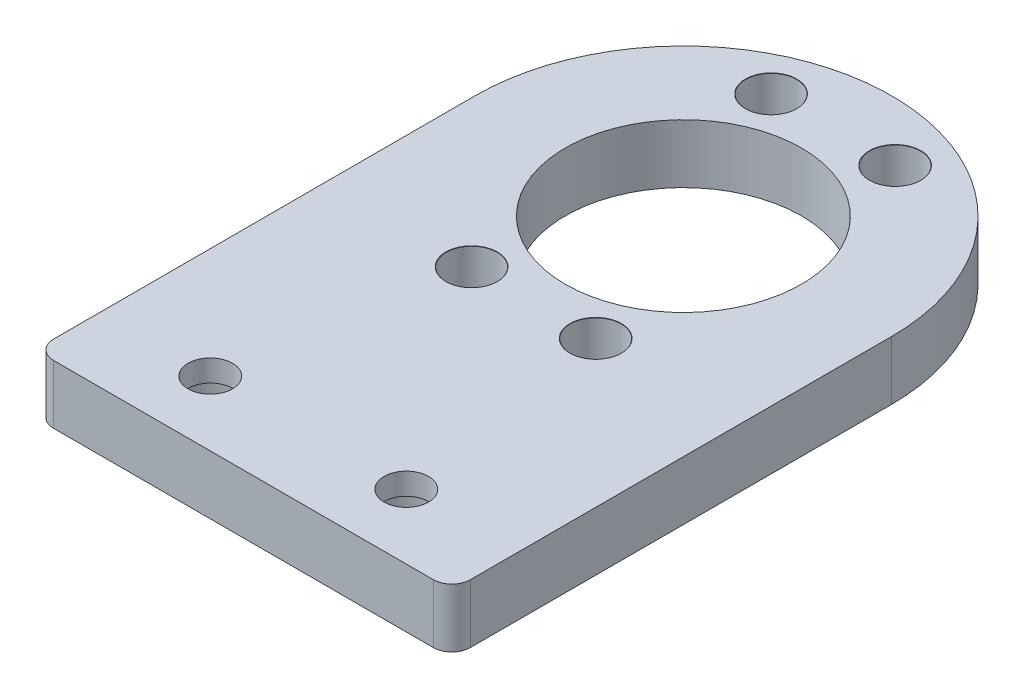
SolidWorks part; units mm, degrees
material "ABS PC"
ref_plane "Front Plane" through (0, 0, 0) normal (0, 0, 1) x (1, 0, 0)
ref_plane "Top Plane" through (0, 0, 0) normal (0, 1, 0) x (1, 0, 0)
ref_plane "Right Plane" through (0, 0, 0) normal (1, 0, 0) x (0, 0, -1)
sketch "Sketch1" plane through (0, 0, 0) normal (0, 1, 0) x (1, 0, 0)
  line L5 (-22.5, -47.5) -> (22.5, -47.5)
  line L6 (-22.5, -47.5) -> (-22.5, 0)
  line L8 (22.5, -47.5) -> (22.5, 0)
  line L9 (-22.5, -47.5) -> (22.5, 0) construction
  line L10 (-22.5, 0) -> (22.5, -47.5) construction
  arc A0 (22.5, 0) -> (-22.5, 0) centre (0, 0) ccw
  point P2 (0, -23.75)
  dimension "D1" = 45
  dimension "D2" = 70
  dimension "D3" = 45
extrude "Boss-Extrude1" add sketch "Sketch1" along normal blind 6.35
sketch "Sketch2" plane through (0, 6.35, 0) normal (0, 1, 0) x (1, 0, 0)
  line L0 (-6.697, 16.1679) -> (6.697, 16.1679) construction
  circle A0 centre (0, 0) radius 17.5 construction
  circle A1 centre (0, 0) radius 17.5 construction
  circle A2 centre (0, 0) radius 17.5 construction
  circle A3 centre (0, 0) radius 17.5 construction
  circle A4 centre (0, 0) radius 17.5 construction
  circle A5 centre (0, 0) radius 17.5 construction
  circle A6 centre (0, 0) radius 17.5 construction
  circle A7 centre (0, 0) radius 17.5 construction
  point P3 (-6.697, 16.1679)
  point P5 (-16.1679, -6.697)
  point P7 (6.697, 16.1679)
  point P9 (16.1679, 6.697)
  point P11 (16.1679, -6.697)
  point P13 (6.697, -16.1679)
  point P15 (-6.697, -16.1679)
  point P16 (0, 0)
  point P18 (-16.1679, 6.697)
  dimension "D1" = 35
  dimension "D2" = 8
hole_wizard "M5 Clearance Hole1" positions "Sketch3" profile "Sketch4" hole size "M5" standard "ANSI Metric" end condition through all
sketch "Sketch3" plane through (0, 6.35, 0) normal (0, 1, 0) x (1, 0, 0)
  point P0 (-6.697, -16.1679)
  point P3 (6.697, -16.1679)
  point P6 (6.697, 16.1679)
  point P15 (-6.697, 16.1679)
sketch "Sketch4" plane through (-6.697, 6.35, 16.1679) normal (1, 0, 0) x (0, 0, 1)
  line L0 (0, 0) -> (0, 6.35)
  line L1 (0, 6.35) -> (2.75, 6.35)
  line L2 (2.75, 6.35) -> (2.75, 0.025)
  line L3 (2.75, 0.025) -> (2.775, 0)
  line L5 (2.775, 0) -> (0, 0)
  line L6 (-2.75, 0.025) -> (-2.775, 0) construction
  line L11 (0, -6.35) -> (0, 107.95) construction
  dimension "Thru Hole Dia." = 5.5
  dimension "Thru Hole Depth" = 6.35
  dimension "Near C'Sink Dia." = 5.55
  dimension "Near C'Sink Angle" = 90
sketch "Sketch5" plane through (0, 6.35, 0) normal (0, 1, 0) x (1, 0, 0)
  circle A0 centre (0, 0) radius 12.75
  dimension "D1" = 25.5
extrude "Cut-Extrude1" cut sketch "Sketch5" against normal through all
sketch "Sketch6" [suppressed] plane through (0, 6.35, 0) normal (0, 1, 0) x (1, 0, 0)
  line L0 (-22.5, -77.5) -> (22.5, -77.5) construction
  circle A0 centre (0, -71) radius 3.3782
  dimension "D1" = 6.7564
  dimension "D2" = 6.5
sketch "Sketch7" [suppressed] plane through (0, 6.35, 0) normal (0, 1, 0) x (1, 0, 0)
  line L0 (12.5, -58.5) -> (-12.5, -58.5) construction
  line L1 (12.5, -63) -> (-12.5, -63)
  line L2 (12.5, -54) -> (-12.5, -54)
  line L3 (0, -71) -> (0, 0) construction
  line L4 (12.5, -42.5) -> (-12.5, -42.5) construction
  line L5 (12.5, -47) -> (-12.5, -47)
  line L6 (12.5, -38) -> (-12.5, -38)
  line L7 (12.5, -26.5) -> (-12.5, -26.5) construction
  line L8 (12.5, -31) -> (-12.5, -31)
  line L9 (12.5, -22) -> (-12.5, -22)
  arc A0 (12.5, -63) -> (12.5, -54) centre (12.5, -58.5) ccw
  arc A1 (-12.5, -54) -> (-12.5, -63) centre (-12.5, -58.5) ccw
  arc A2 (12.5, -47) -> (12.5, -38) centre (12.5, -42.5) ccw
  arc A3 (-12.5, -38) -> (-12.5, -47) centre (-12.5, -42.5) ccw
  arc A4 (12.5, -31) -> (12.5, -22) centre (12.5, -26.5) ccw
  arc A5 (-12.5, -22) -> (-12.5, -31) centre (-12.5, -26.5) ccw
  circle A6 centre (0, -71) radius 3.3782 construction
  point P2 (0, -58.5)
  point P15 (0, -42.5)
  point P22 (0, -26.5)
  point P28 (0, -63)
  dimension "D2" = 4.5
  dimension "D4" = 8
  dimension "D3" = 25
  dimension "D1" = 3
extrude "Cut-Extrude3" [suppressed] cut sketch "Sketch7" against normal through all
sketch "Sketch8" plane through (0, 0, 0) normal (0, -1, 0) x (1, 0, 0)
  line L0 (10.5848, 40.5) -> (-10.5848, 40.5) construction
  line L1 (-22.5, 47.5) -> (22.5, 47.5) construction
  point P2 (0, 40.5)
  point P5 (0, 47.5)
  dimension "D1" = 7
  dimension "D2" = 21.1696
hole_wizard "CBORE for M4 SHCS1" positions "Sketch9" profile "Sketch10" counterbore size "M4" standard "ANSI Metric" end condition through all
sketch "Sketch9" plane through (0, 0, 0) normal (0, -1, 0) x (-1, 0, 0)
  point P0 (-10.5848, -40.5)
  point P3 (10.5848, -40.5)
sketch "Sketch10" plane through (10.5848, 0, 40.5) normal (1, 0, 0) x (0, 0, -1)
  line L0 (0, 0) -> (0, 6.35)
  line L1 (0, 6.35) -> (2.4, 6.35)
  line L3 (2.4, 6.35) -> (2.4, 4)
  line L4 (4, 4) -> (2.4, 4)
  line L5 (4, 4) -> (4, 0.025)
  line L6 (4, 0.025) -> (4.025, 0)
  line L7 (4.025, 0) -> (0, 0)
  line L8 (-4, 0.025) -> (-4.025, 0) construction
  line L11 (0, -6.35) -> (0, 107.95) construction
  dimension "Thru Hole Dia." = 4.8
  dimension "Thru Hole Depth" = 6.35
  dimension "C'Bore Dia." = 8
  dimension "C'Bore Depth" = 4
  dimension "Near C'Sink Dia." = 8.05
  dimension "Near C'Sink Angle" = 90
fillet "Fillet1" radius 2 2 edges at (-22.5, 3.175, 47.5) (22.5, 3.175, 47.5)
